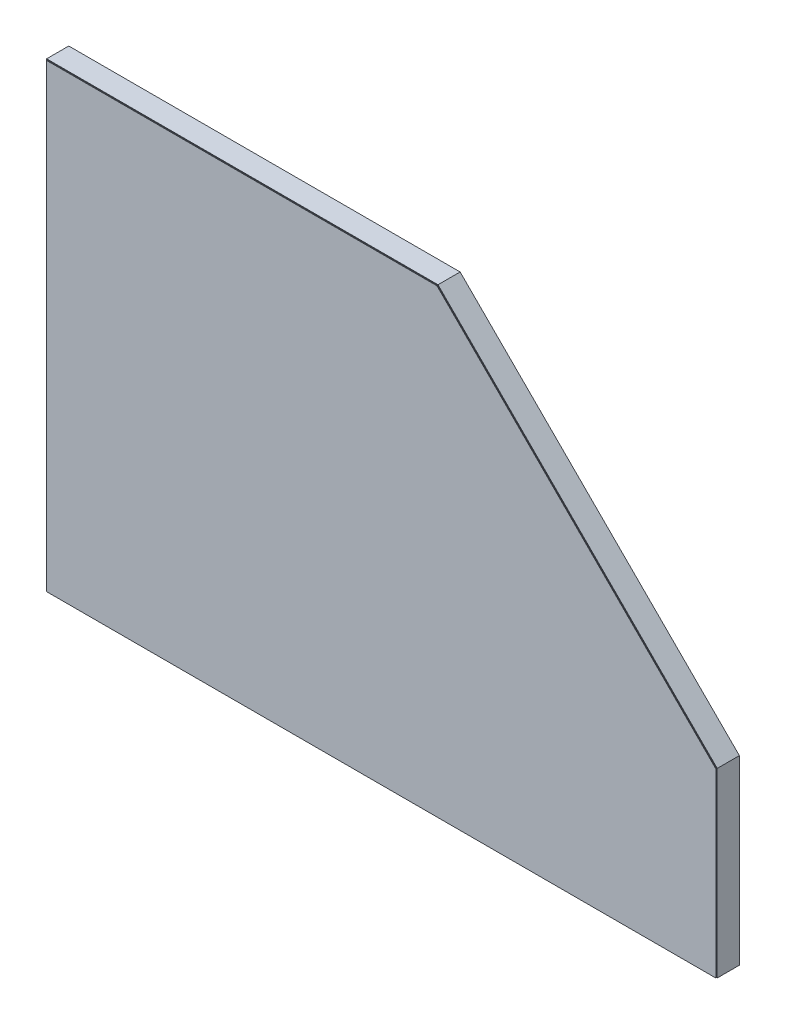
SolidWorks part; units mm, degrees
other "Elemento de detalle1"
other "Carpeta de soldadura"
other "Cordón de soldadura1"
ref_plane "Alzado" through (0, 0, 0) normal (0, 0, 1) x (1, 0, 0)
ref_plane "Planta" through (0, 0, 0) normal (0, 1, 0) x (1, 0, 0)
ref_plane "Vista lateral" through (0, 0, 0) normal (1, 0, 0) x (0, 0, -1)
sketch "Croquis1" plane through (0, 0, 0) normal (0, 0, 1) x (1, 0, 0)
  line L0 (0, 0) -> (768, 0)
  line L1 (768, 0) -> (768, 208)
  line L2 (768, 208) -> (448, 528)
  line L3 (448, 528) -> (0, 528)
  line L4 (0, 528) -> (0, 0)
  dimension "D1" = 768
  dimension "D2" = 208
  dimension "D3" = 448
  dimension "D4" = 528
extrude "Saliente-Extruir1" add sketch "Croquis1" along normal blind 0.8357
sketch "Croquis3" plane through (0, 0, 0) normal (0, 0, -1) x (-1, 0, 0)
  line L0 (0.8357, 0) -> (0.8357, 528.8357)
  line L1 (0.8357, 528.8357) -> (-448.3461, 528.8357)
  line L2 (-448.3461, 528.8357) -> (-768.8357, 208.3461)
  line L3 (-768.8357, 208.3461) -> (-768.8357, 0)
  line L4 (0.8357, 0) -> (0, 0)
  line L5 (0, 0) -> (0, 528)
  line L6 (0, 528) -> (-448, 528)
  line L7 (-448, 528) -> (-768, 208)
  line L8 (-768, 208) -> (-768, 0)
  line L9 (-768, 0) -> (0, 0)
  line L10 (0, 0) -> (0, 528)
  line L11 (0, 528) -> (-448, 528)
  line L12 (-448, 528) -> (-768, 208)
  line L13 (-768, 208) -> (-768, 0)
  line L15 (-768, 0) -> (-768.8357, 0)
  dimension "D1" = 0
  dimension "D2" = 0.8357
extrude "Saliente-Extruir2" add sketch "Croquis3" along normal blind 25.4 separate body
